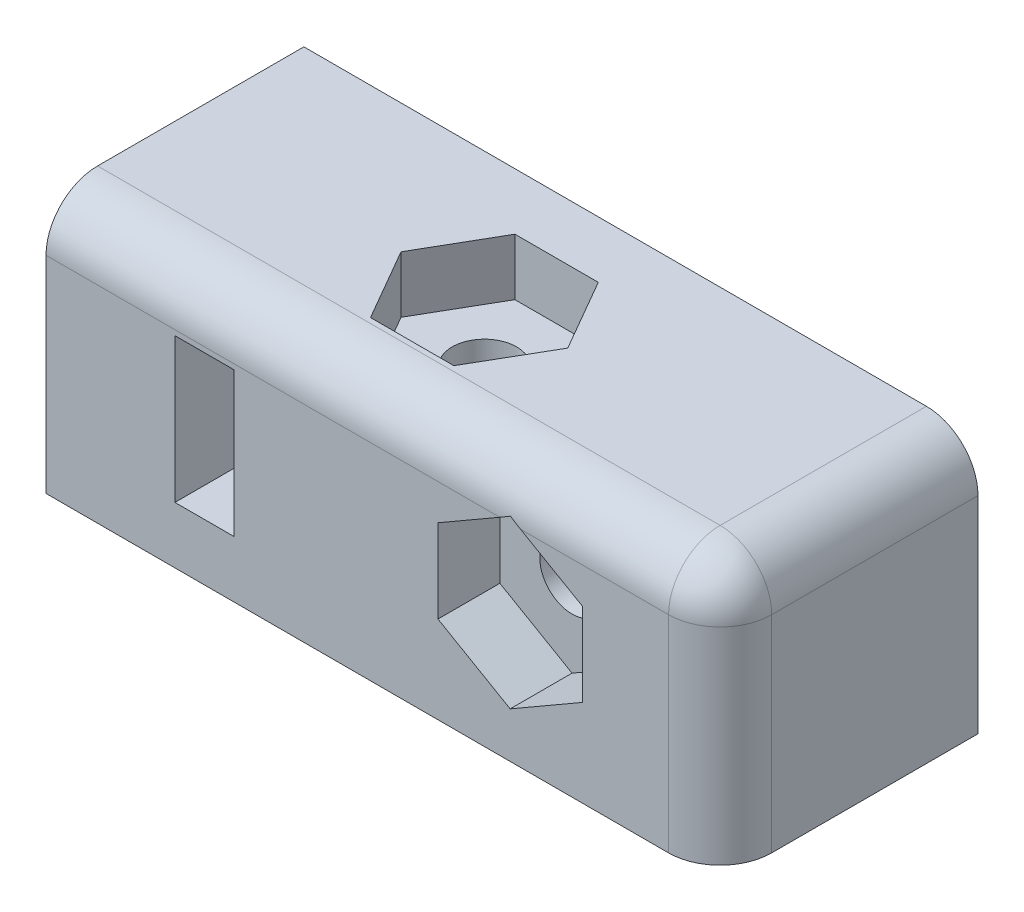
SolidWorks part; units mm, degrees
ref_plane "Front Plane" through (0, 0, 0) normal (0, 0, 1) x (1, 0, 0)
ref_plane "Top Plane" through (0, 0, 0) normal (0, 1, 0) x (1, 0, 0)
ref_plane "Right Plane" through (0, 0, 0) normal (1, 0, 0) x (0, 0, -1)
sketch "Sketch1" plane through (0, 0, 0) normal (0, 1, 0) x (1, 0, 0)
  line L1 (0, 0) -> (74.5, 0)
  line L2 (0, 0) -> (0, 10)
  line L3 (0, 10) -> (74.5, 10)
  line L4 (74.5, 0) -> (74.5, 10)
  dimension "D1" = 74.5
  dimension "D2" = 10
extrude "Boss-Extrude1" add sketch "Sketch1" along normal blind 10
sketch "Sketch2" plane through (0, 10, 0) normal (0, 1, 0) x (1, 0, 0)
  line L0 (0, 5) -> (74.5, 5) construction
  line L1 (0, 10) -> (0, 0) construction
  line L2 (74.5, 0) -> (74.5, 10) construction
  circle A0 centre (12, 5) radius 1.25
  circle A1 centre (62.5, 5) radius 1.25
  dimension "D3" = 2.5
  dimension "D4" = 2.5
  dimension "D1" = 12
  dimension "D2" = 12
extrude "Cut-Extrude1" cut sketch "Sketch2" against normal blind 10
sketch "Sketch3" plane through (0, 0, -10) normal (0, 0, -1) x (-1, 0, 0)
  line L0 (-74.5, 5) -> (0, 5) construction
  line L1 (-74.5, 10) -> (-74.5, 0) construction
  line L2 (0, 10) -> (0, 0) construction
  circle A0 centre (-56.5, 5) radius 1.25
  circle A1 centre (-18, 5) radius 1.25
  dimension "D1" = 2.5
  dimension "D2" = 2.5
  dimension "D3" = 18
  dimension "D4" = 18
extrude "Cut-Extrude2" cut sketch "Sketch3" against normal blind 10
sketch "Sketch4" plane through (74.5, 0, 0) normal (1, 0, 0) x (0, 0, -1)
  line L0 (5, 10) -> (5, 4.1725) construction
  line L1 (0, 10) -> (10, 10) construction
  line L2 (0, 5) -> (5.9702, 5) construction
  line L3 (0, 10) -> (0, 0) construction
  circle A0 centre (5, 5) radius 1.25
  dimension "D1" = 2.5
extrude "Cut-Extrude3" cut sketch "Sketch4" against normal blind 5
sketch "Sketch5" plane through (0, 0, 0) normal (-1, 0, 0) x (0, 0, 1)
  line L0 (-5, 10) -> (-5, 0) construction
  line L1 (-10, 10) -> (0, 10) construction
  line L2 (-10, 0) -> (0, 0) construction
  line L3 (-10, 5) -> (0, 5) construction
  line L4 (-10, 10) -> (-10, 0) construction
  line L5 (0, 10) -> (0, 0) construction
  circle A0 centre (-5, 5) radius 1.25
  dimension "D1" = 2.5
extrude "Cut-Extrude4" cut sketch "Sketch5" against normal blind 5
sketch "Sketch6" plane through (0, 10, 0) normal (0, 1, 0) x (1, 0, 0)
  line L0 (74.5, 10) -> (0, 10) construction
  line L1 (13.6166, 2.2) -> (15.2332, 5)
  line L2 (15.2332, 5) -> (13.6166, 7.8)
  line L3 (13.6166, 7.8) -> (10.3834, 7.8)
  line L4 (10.3834, 7.8) -> (8.7668, 5)
  line L5 (8.7668, 5) -> (10.3834, 2.2)
  line L6 (10.3834, 2.2) -> (13.6166, 2.2)
  circle A0 centre (12, 5) radius 2.8 construction
  dimension "D1" = 5.6
extrude "Cut-Extrude5" cut sketch "Sketch6" against normal blind 2.2
sketch "Sketch7" plane through (0, 10, 0) normal (0, 1, 0) x (1, 0, 0)
  line L0 (74.5, 10) -> (0, 10) construction
  line L1 (60.8834, 7.8) -> (59.2668, 5)
  line L2 (59.2668, 5) -> (60.8834, 2.2)
  line L3 (60.8834, 2.2) -> (64.1166, 2.2)
  line L4 (64.1166, 2.2) -> (65.7332, 5)
  line L5 (65.7332, 5) -> (64.1166, 7.8)
  line L6 (64.1166, 7.8) -> (60.8834, 7.8)
  circle A0 centre (62.5, 5) radius 2.8 construction
  dimension "D1" = 5.6
extrude "Cut-Extrude6" cut sketch "Sketch7" against normal blind 2.2
sketch "Sketch9" plane through (0, 0, 0) normal (0, 0, 1) x (1, 0, 0)
  line L1 (58.1166, 7.8) -> (54.8834, 7.8)
  line L2 (54.8834, 7.8) -> (53.2668, 5)
  line L3 (53.2668, 5) -> (54.8834, 2.2)
  line L4 (54.8834, 2.2) -> (58.1166, 2.2)
  line L5 (58.1166, 2.2) -> (59.7332, 5)
  line L6 (59.7332, 5) -> (58.1166, 7.8)
  circle A0 centre (56.5, 5) radius 2.8 construction
  dimension "D1" = 5.6
extrude "Cut-Extrude8" cut sketch "Sketch9" against normal blind 2.2
sketch "Sketch11" plane through (0, 0, 0) normal (0, 0, 1) x (1, 0, 0)
  line L0 (0, 5) -> (74.5, 5) construction
  line L1 (0, 10) -> (0, 0) construction
  line L2 (74.5, 10) -> (74.5, 0) construction
  line L4 (5, 2.2) -> (7.3, 2.2)
  line L5 (5, 2.2) -> (5, 7.8)
  line L6 (5, 7.8) -> (7.3, 7.8)
  line L7 (7.3, 2.2) -> (7.3, 7.8)
  line L8 (5, 2.2) -> (7.3, 7.8) construction
  line L9 (5, 7.8) -> (7.3, 2.2) construction
  line L10 (67.2, 2.2) -> (69.5, 2.2)
  line L11 (67.2, 2.2) -> (67.2, 7.8)
  line L12 (67.2, 7.8) -> (69.5, 7.8)
  line L13 (69.5, 2.2) -> (69.5, 7.8)
  line L14 (67.2, 2.2) -> (69.5, 7.8) construction
  line L15 (67.2, 7.8) -> (69.5, 2.2) construction
  point P6 (6.15, 5)
  point P11 (68.35, 5)
  dimension "D1" = 2.3
  dimension "D2" = 5.6
  dimension "D3" = 2.3
  dimension "D4" = 5.6
  dimension "D5" = 5
  dimension "D6" = 5
extrude "Cut-Extrude9" cut sketch "Sketch11" against normal blind 7.3
sketch "Sketch12" plane through (0, 0, 0) normal (0, 0, 1) x (1, 0, 0)
  line L1 (118.9376, 29.7047) -> (26.1416, 29.7047)
  line L2 (118.9376, 29.7047) -> (118.9376, -5.4838)
  line L3 (118.9376, -5.4838) -> (26.1416, -5.4838)
  line L4 (26.1416, 29.7047) -> (26.1416, -5.4838)
  line L5 (118.9376, 29.7047) -> (26.1416, -5.4838) construction
  line L6 (118.9376, -5.4838) -> (26.1416, 29.7047) construction
  point P0 (72.5396, 12.1105)
extrude "Cut-Extrude10" cut sketch "Sketch12" against normal blind 14
sketch "Sketch13" plane through (0, 0, 0) normal (0, 0, 1) x (1, 0, 0)
  line L1 (20.8, 6.6166) -> (18, 8.2332)
  line L2 (18, 8.2332) -> (15.2, 6.6166)
  line L3 (15.2, 6.6166) -> (15.2, 3.3834)
  line L4 (15.2, 3.3834) -> (18, 1.7668)
  line L5 (18, 1.7668) -> (20.8, 3.3834)
  line L6 (20.8, 3.3834) -> (20.8, 6.6166)
  circle A0 centre (18, 5) radius 2.8 construction
  dimension "D1" = 5.6
extrude "Cut-Extrude11" cut sketch "Sketch13" against normal blind 2.4
ref_plane "Plane1" through (26.1416, 10, 0) normal (1, 0, 0) x (0, 0, -1)
fillet "Fillet1" radius 2 1 edges at (26.1416, 5, 0)
fillet "Fillet2" radius 2 3 edges at (12.0708, 10, 0) (25.5558, 10, -0.5858) (26.1416, 10, -6)
